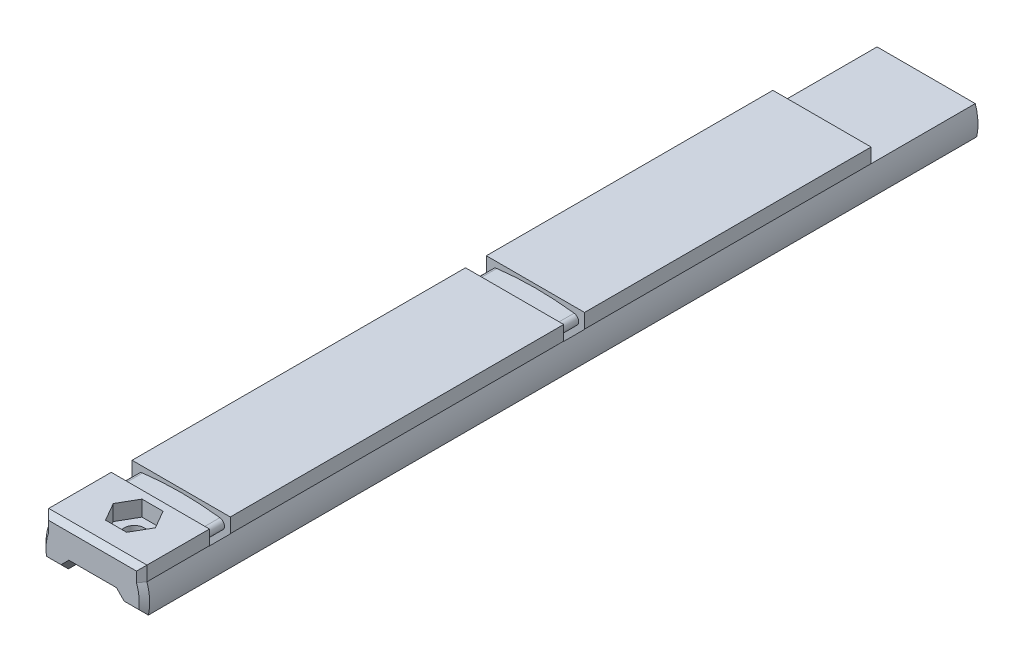
SolidWorks part; units mm, degrees
ref_plane "정면" through (0, 0, 0) normal (0, 0, 1) x (1, 0, 0)
ref_plane "윗면" through (0, 0, 0) normal (0, 1, 0) x (1, 0, 0)
ref_plane "우측면" through (0, 0, 0) normal (1, 0, 0) x (0, 0, -1)
sketch "스케치1" plane through (0, 0, 0) normal (0, 0, 1) x (1, 0, 0)
  line L0 (-9.4248, 3.19) -> (9.4248, 3.19)
  line L1 (5.65, -2.21) -> (9.7015, -2.21)
  line L2 (-4.15, -0.71) -> (-5.65, -2.21)
  line L3 (-5.65, -2.21) -> (-9.7015, -2.21)
  line L4 (0, 0) -> (0, -11.2422) construction
  line L5 (-4.15, -0.71) -> (4.15, -0.71)
  line L6 (4.15, -0.71) -> (5.65, -2.21)
  arc A0 (-9.4248, 3.19) -> (-9.7015, -2.21) centre (0, 0) ccw
  arc A1 (9.7015, -2.21) -> (9.4248, 3.19) centre (0, 0) ccw
  dimension "D1" = 9.95
  dimension "D2" = 3.9
  dimension "D3" = 8.3
  dimension "D4" = 135
  dimension "D5" = 0.71
  dimension "D6" = 1.5
extrude "보스-돌출1" add sketch "스케치1" along normal blind 160
sketch "스케치4" plane through (0, 3.19, 0) normal (0, 1, 0) x (1, 0, 0)
  line L0 (9.4248, 0) -> (-9.4248, 0) construction
  line L1 (-9.4248, -20) -> (9.4248, -20)
  line L2 (-9.4248, -20) -> (-9.4248, -160)
  line L3 (-9.4248, -160) -> (9.4248, -160)
  line L4 (9.4248, -20) -> (9.4248, -160)
  dimension "D1" = 20
extrude "보스-돌출2" add sketch "스케치4" along normal blind 2.78
sketch "스케치5" plane through (0, 0, 0) normal (0, 1, 0) x (1, 0, 0)
  line L0 (0, -152) -> (0, 0) construction
  circle A0 centre (0, -152) radius 1.95
  dimension "D1" = 3.9
  dimension "D2" = 152
extrude "컷-돌출2" cut sketch "스케치5" against normal through all both and the other way through all
sketch "스케치6" plane through (0, 5.97, 0) normal (0, 1, 0) x (1, 0, 0)
  line L1 (4.0415, -152) -> (2.0207, -148.5)
  line L2 (2.0207, -148.5) -> (-2.0207, -148.5)
  line L3 (-2.0207, -148.5) -> (-4.0415, -152)
  line L4 (-4.0415, -152) -> (-2.0207, -155.5)
  line L5 (-2.0207, -155.5) -> (2.0207, -155.5)
  line L6 (2.0207, -155.5) -> (4.0415, -152)
  circle A0 centre (0, -152) radius 3.5 construction
  dimension "D1" = 7
extrude "컷-돌출3" cut sketch "스케치6" against normal blind 3
chamfer "모따기1" distance 1 angle 45 10 edges at (0, -0.71, 160) (-4.9, -1.46, 160) (-7.6757, -2.21, 160) (-9.937, 0.5092, 160) (-9.4248, 4.58, 160) (0, 5.97, 160) (9.4248, 4.58, 160) (9.937, 0.5092, 160) (7.6757, -2.21, 160) (4.9, -1.46, 160)
sketch "스케치8" plane through (1.72, 1.72, 0) normal (-0.7071, -0.7071, 0) x (0, 0, 1)
  line L0 (159, -3.4365) -> (0, -3.4365) construction
  line L1 (75, -3.4365) -> (79, -3.4365)
  line L2 (75, -3.4365) -> (75, -4.4365)
  line L3 (75, -4.4365) -> (79, -4.4365)
  line L4 (79, -3.4365) -> (79, -4.4365)
  dimension "D1" = 4
  dimension "D2" = 1
  dimension "D3" = 75
extrude "컷-돌출4" cut sketch "스케치8" against normal through all
mirror "대칭 복사1" about plane through (0, 0, 0) normal (1, 0, 0) of "컷-돌출4"
sketch "스케치9" plane through (0, 0, 75) normal (0, 0, 1) x (1, 0, 0)
  line L0 (-9.4248, 4.5648) -> (-13.2918, 9.7839)
  line L1 (-13.2918, 9.7839) -> (12.3285, 9.7839)
  line L2 (12.3285, 9.7839) -> (9.4248, 4.5648)
  arc A0 (-9.4248, 4.5648) -> (9.4248, 4.5648) centre (0, -54.5292) cw
extrude "컷-돌출5" cut sketch "스케치9" along normal blind 4
fillet "필렛1" radius 1 2 edges at (9.4248, 4.5648, 77) (-9.4248, 4.5648, 77)
pattern_linear "선형 패턴1" count 2 spacing 68 along (0, 0, 1) of "컷-돌출4", "대칭 복사1", "컷-돌출5", "필렛1"
